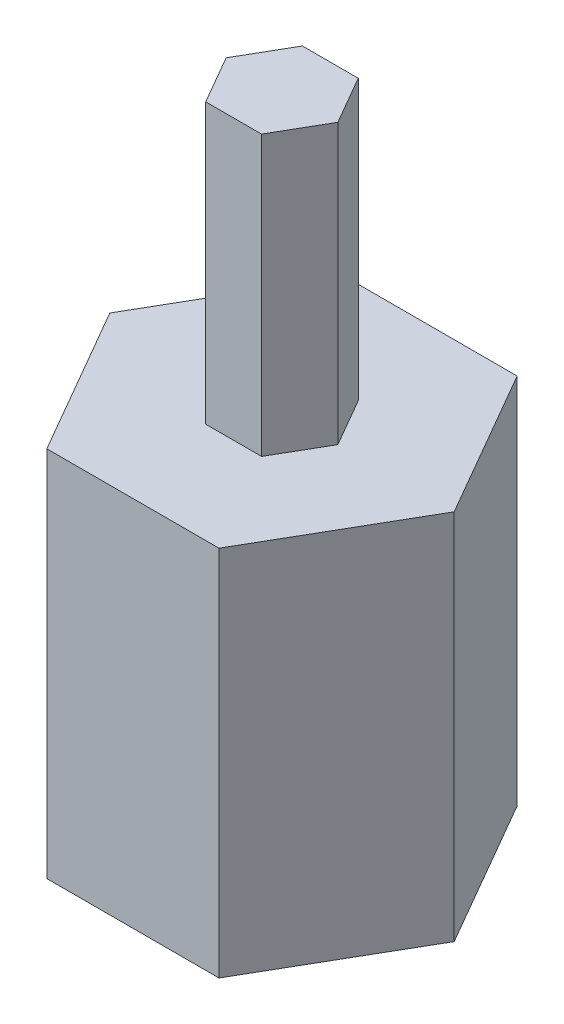
SolidWorks part; units mm, degrees
ref_plane "Front Plane" through (0, 0, 0) normal (0, 0, 1) x (1, 0, 0)
ref_plane "Top Plane" through (0, 0, 0) normal (0, 1, 0) x (1, 0, 0)
ref_plane "Right Plane" through (0, 0, 0) normal (1, 0, 0) x (0, 0, -1)
sketch "Sketch1" plane through (0, 0, 0) normal (0, 1, 0) x (1, 0, 0)
  line L1 (1.2, 0) -> (0.6, 1.0392)
  line L2 (0.6, 1.0392) -> (-0.6, 1.0392)
  line L3 (-0.6, 1.0392) -> (-1.2, 0)
  line L4 (-1.2, 0) -> (-0.6, -1.0392)
  line L5 (-0.6, -1.0392) -> (0.6, -1.0392)
  line L6 (0.6, -1.0392) -> (1.2, 0)
  circle A0 centre (0, 0) radius 1.0392 construction
  dimension "D1" = 1.2
extrude "Boss-Extrude1" add sketch "Sketch1" along normal blind 6
sketch "Sketch2" plane through (0, 0, 0) normal (0, -1, 0) x (1, 0, 0)
  line L1 (3.7, 0) -> (1.85, 3.2043)
  line L2 (1.85, 3.2043) -> (-1.85, 3.2043)
  line L3 (-1.85, 3.2043) -> (-3.7, 0)
  line L4 (-3.7, 0) -> (-1.85, -3.2043)
  line L5 (-1.85, -3.2043) -> (1.85, -3.2043)
  line L6 (1.85, -3.2043) -> (3.7, 0)
  circle A0 centre (0, 0) radius 3.2043 construction
  circle A1 centre (0, 0) radius 3.7 construction
  dimension "D1" = 7.4
extrude "Boss-Extrude2" add sketch "Sketch2" along normal blind 8
